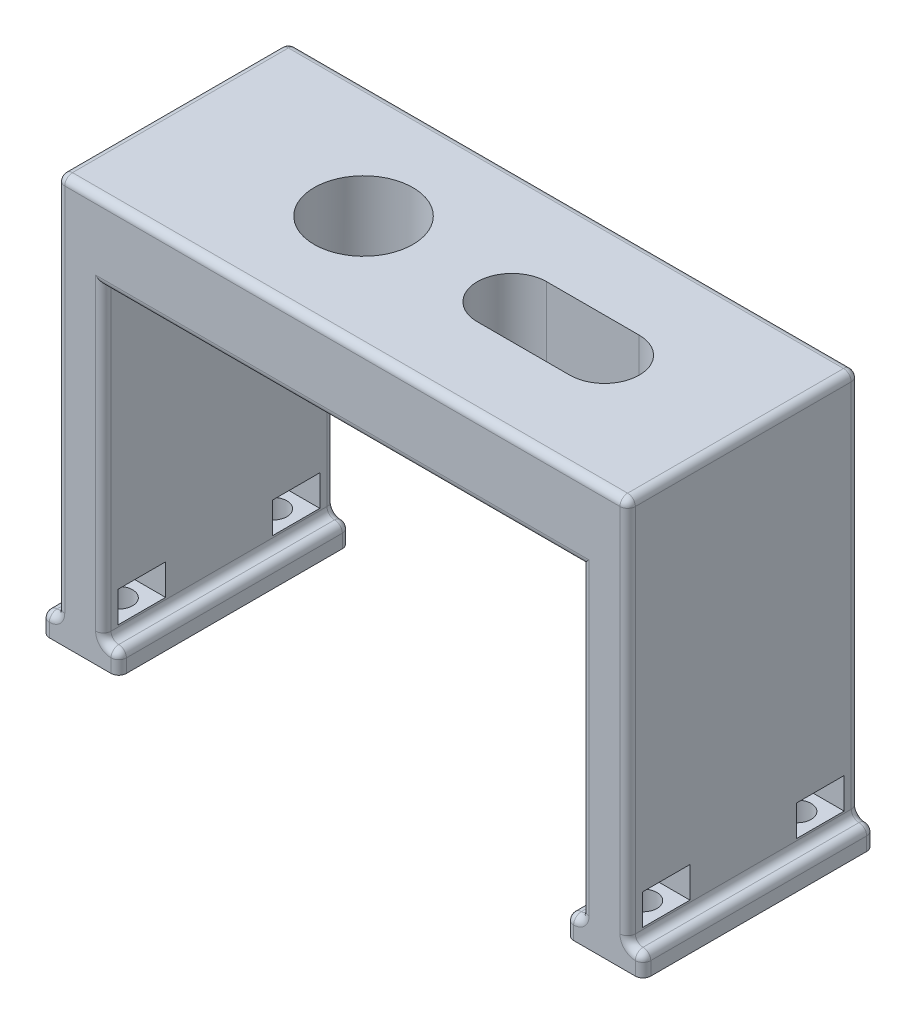
SolidWorks part; units mm, degrees
ref_plane "Front Plane" through (0, 0, 0) normal (0, 0, 1) x (1, 0, 0)
ref_plane "Top Plane" through (0, 0, 0) normal (0, 1, 0) x (1, 0, 0)
ref_plane "Right Plane" through (0, 0, 0) normal (1, 0, 0) x (0, 0, -1)
sketch "Sketch1" plane through (0, 0, 0) normal (0, 1, 0) x (1, 0, 0)
  line L1 (0, 0) -> (74, 0)
  line L2 (0, 0) -> (0, 30)
  line L3 (0, 30) -> (74, 30)
  line L4 (74, 0) -> (74, 30)
  dimension "D1" = 74
  dimension "D2" = 30
extrude "Boss-Extrude1" add sketch "Sketch1" along normal blind 10
sketch "Sketch2" plane through (0, 10, 0) normal (0, 1, 0) x (1, 0, 0)
  line L0 (0, 30) -> (0, 0) construction
  line L1 (74, 30) -> (0, 30) construction
  circle A0 centre (24.75, 15) radius 6.4
  dimension "D1" = 12.8
  dimension "D2" = 24.75
  dimension "D3" = 15
extrude "Cut-Extrude1" cut sketch "Sketch2" against normal blind 15
sketch "Sketch3" plane through (0, 0, 0) normal (0, 0, 1) x (1, 0, 0)
  line L0 (6, -40) -> (8, -40)
  line L1 (0, 0) -> (6, 0)
  line L2 (0, 0) -> (0, -40)
  line L4 (6, 0) -> (6, -40)
  line L5 (-2, -40) -> (0, -40)
  line L6 (-2, -40) -> (-2, -42.75)
  line L7 (-2, -42.75) -> (8, -42.75)
  line L8 (8, -40) -> (8, -42.75)
  dimension "D1" = 10
  dimension "D2" = 6
  dimension "D3" = 2
  dimension "D4" = 40
  dimension "D5" = 2.75
extrude "Boss-Extrude2" add sketch "Sketch3" against normal blind 30
hole_wizard "M3 Clearance Hole1" positions "Sketch7" profile "Sketch9" hole size "M3" standard "ANSI Metric"
sketch "Sketch7" plane through (0, -42.75, 0) normal (0, -1, 0) x (-1, 0, 0)
  line L0 (2, 0) -> (-8, 0) construction
  line L1 (2, 30) -> (-8, 30) construction
  line L2 (2, 30) -> (2, 0) construction
  point P0 (-3, 5)
  point P2 (-3, 25)
  dimension "D1" = 5
  dimension "D2" = 5
  dimension "D3" = 5
  dimension "D4" = 5
sketch "Sketch9" plane through (3, -42.75, -5) normal (1, 0, 0) x (0, 0, -1)
  line L0 (0, 0) -> (0, 11.0815)
  line L1 (0, 11.0815) -> (1.8, 10)
  line L2 (1.8, 10) -> (1.8, 0)
  line L5 (1.8, 0) -> (0, 0)
  line L10 (0, 11.0815) -> (-1.8, 10) construction
  line L11 (0, -6.35) -> (0, 107.95) construction
  dimension "Hole Dia." = 3.6
  dimension "Hole Depth" = 10
  dimension "Drill Angle" = 118
sketch "Sketch10" plane through (0, 0, 0) normal (-1, 0, 0) x (0, 0, 1)
  line L0 (0, 10) -> (0, -40) construction
  line L1 (-28.08, -34.75) -> (-21.92, -34.75)
  line L2 (-28.08, -34.75) -> (-28.08, -38.75)
  line L3 (-28.08, -38.75) -> (-21.92, -38.75)
  line L4 (-21.92, -34.75) -> (-21.92, -38.75)
  line L5 (-8.08, -34.75) -> (-1.92, -34.75)
  line L6 (-8.08, -34.75) -> (-8.08, -38.75)
  line L7 (-8.08, -38.75) -> (-1.92, -38.75)
  line L8 (-1.92, -34.75) -> (-1.92, -38.75)
  line L9 (-30, 10) -> (-30, -40) construction
  line L10 (-30, -42.75) -> (0, -42.75) construction
  dimension "D1" = 6.16
  dimension "D2" = 6.16
  dimension "D3" = 4
  dimension "D4" = 4
  dimension "D5" = 1.92
  dimension "D6" = 1.92
  dimension "D7" = 4
  dimension "D8" = 4
extrude "Cut-Extrude2" cut sketch "Sketch10" against normal up to next
ref_plane "Plane1" through (37, 0, 0) normal (-1, 0, 0) x (0, 0, 1)
mirror "Mirror1" about plane through (37, 0, 0) normal (-1, 0, 0) of "M3 Clearance Hole1", "Cut-Extrude2", "Boss-Extrude2"
fillet "Fillet1" radius 1 30 edges at (66, -41.375, 0) (76, -41.375, 0) (76, -40, -15) (74, -40, -15) (76, -41.375, -30) (66, -41.375, -30) (68, -40, -15) (66, -40, -15) (8, -41.375, 0) (8, -41.375, -30) (8, -40, -15) (6, -40, -15) (-2, -41.375, -30) (-2, -41.375, 0) (-2, -40, -15) (0, -40, -15) (74, -15, 0) (68, -20, 0) (37, 0, 0) (6, -20, 0) (0, -15, 0) (74, 10, -15) (37, 10, 0) (0, 10, -15) (68, -20, -30) (74, -15, -30) (0, -15, -30) (6, -20, -30) (37, 0, -30) (37, 10, -30)
sketch "Sketch11" plane through (0, 10, 0) normal (0, 1, 0) x (1, 0, 0)
  line L0 (44, 15) -> (56, 15) construction
  line L1 (44, 19.5) -> (56, 19.5)
  line L2 (44, 10.5) -> (56, 10.5)
  line L3 (73, 0) -> (1, 0) construction
  line L5 (74, 1) -> (74, 29) construction
  arc A0 (44, 19.5) -> (44, 10.5) centre (44, 15) ccw
  arc A1 (56, 10.5) -> (56, 19.5) centre (56, 15) ccw
  point P2 (50, 15)
  dimension "D1" = 12
  dimension "D2" = 9
  dimension "D3" = 15
  dimension "D4" = 24
extrude "Cut-Extrude3" cut sketch "Sketch11" against normal up to next
